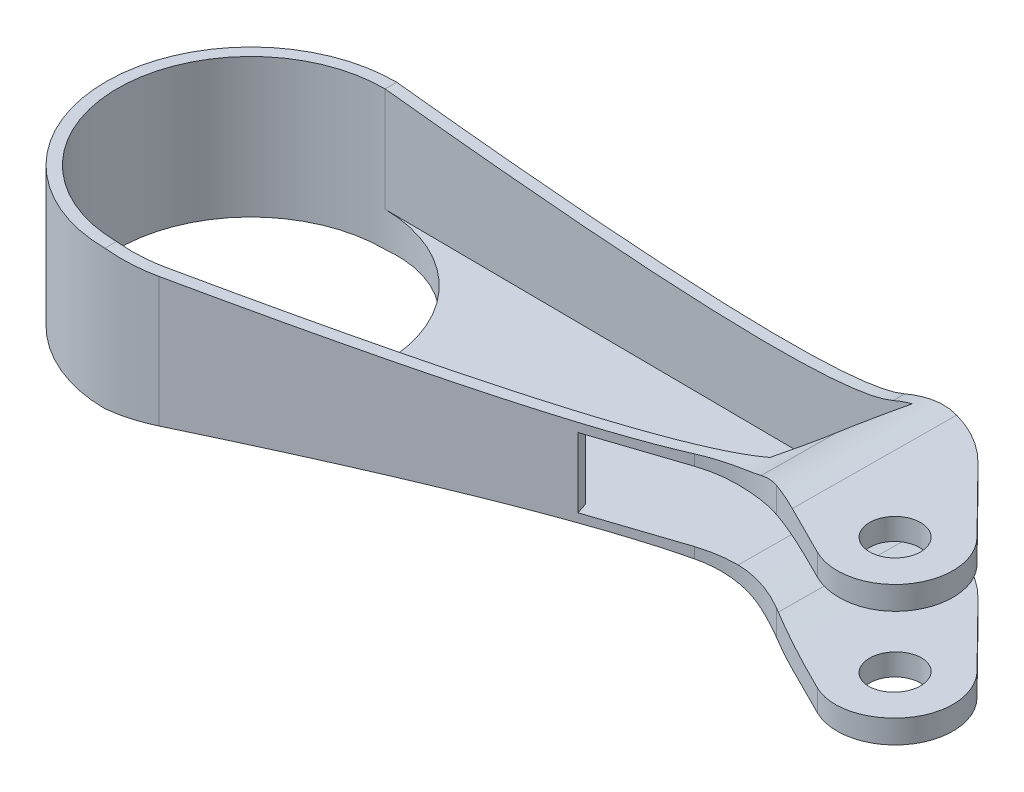
SolidWorks part; units mm, degrees
ref_plane "Front Plane" through (0, 0, 0) normal (0, 0, 1) x (1, 0, 0)
ref_plane "Top Plane" through (0, 0, 0) normal (0, 1, 0) x (1, 0, 0)
ref_plane "Right Plane" through (0, 0, 0) normal (1, 0, 0) x (0, 0, -1)
sketch "Sketch1" plane through (0, 0, 0) normal (0, 1, 0) x (1, 0, 0)
  line L0 (0, 0) -> (278, 0) construction
  line L1 (0, 0) -> (0, 62.5) construction
  line L2 (0.4822, 62.4981) -> (19.6718, -59.3235) construction
  line L3 (295.8135, 17.5408) -> (266.7848, -22.3432) construction
  line L4 (278, 0) -> (278, 25) construction
  line L5 (0.4822, 62.4981) -> (378.2559, 59.5837)
  line L6 (378.2559, 59.5837) -> (19.6718, -59.3235)
  line L7 (266.7848, -22.3432) -> (212.8435, 4.7326)
  line L8 (295.8135, 17.5408) -> (253.4664, 60.5464)
  line L9 (253.4664, 60.5464) -> (212.8435, 4.7326) construction
  circle A0 centre (0, 0) radius 62.5
  circle A1 centre (278, 0) radius 11
  circle A2 centre (278, 0) radius 25
  circle A3 centre (0, 0) radius 57.5
  point P11 (284.898, 28.626)
  dimension "D2" = 125
  dimension "D3" = 22
  dimension "D4" = 50
  dimension "D7" = 115
  dimension "D1" = 278
  dimension "D5" = 135
  dimension "D6" = 135
extrude "Boss-Extrude2" add sketch "Sketch1" along normal blind 30 and the other way blind 30 contours A0 A3 | A2 L8 L6 | A2 L6 L7 | A0 L6 L8 L5 | A2 A1 region at (142.126, 0, -22.2097) region at (43.1095, 0, -42.7782) region at (284.0848, 0, -25.2513) region at (241.7938, 0, -2.6298) region at (283.6909, 0, -23.6169)
fillet "Fillet1" radius 50 2 edges at (212.8435, 0, -4.7326) (253.4664, 0, -60.5464)
sketch "Sketch4" plane through (158.9581, 0, -156.5242) normal (0.7125, 0, -0.7016) x (-0.7016, 0, -0.7125)
  line L0 (-296.311, 0) -> (0, 0) construction
  line L1 (-179.7518, 87.9908) -> (-179.7518, -107.4173) construction
  line L2 (-120.0533, 10) -> (-120.0533, -10)
  line L3 (-120.0533, 10) -> (-276.8636, 10)
  line L4 (-120.0533, -10) -> (-276.8636, -10)
  line L5 (-276.8636, 10) -> (-276.8636, -10)
  line L6 (-120.0533, 30) -> (-120.0533, -30) construction
  dimension "D1" = 20
  dimension "D2" = 10
extrude "Cut-Extrude1" cut sketch "Sketch4" against normal blind 100
sketch "Sketch5" plane through (0, 30, 0) normal (0, 1, 0) x (1, 0, 0)
  line L0 (18.098, -54.5776) -> (213.7011, 10.2848)
  line L1 (229.7147, 55.7295) -> (213.7011, 10.2848)
  line L2 (193.1854, -1.786) -> (19.6718, -59.3235) construction
  line L3 (0.4436, 57.4983) -> (229.7147, 55.7295)
  line L5 (0.4822, 62.4981) -> (232.7563, 60.7062) construction
  arc A0 (0.4436, 57.4983) -> (0, -57.5) centre (0, 0) cw
  circle A1 centre (0, 0) radius 57.5 construction
  point P7 (213.8584, 9.8227)
  point P11 (0, 0)
  circle M11 centre (0, 0) radius 57.5
  dimension "D1" = 5
  dimension "D2" = 5
extrude "Cut-Extrude2" cut sketch "Sketch5" against normal blind 45 contours L3 L0 M11 region at (122.2864, 30, -19.5353)
sketch "Sketch6" plane through (0.4822, 0, -62.4981) normal (0.0077, 0, -1) x (-1, 0, -0.0077)
  line L0 (0, 0) -> (-302.9917, 0) construction
  line L1 (-227.281, -30) -> (-227.281, 30)
  line L2 (0, -30) -> (-232.281, -30) construction
  line L3 (0, 30) -> (-232.281, 30) construction
  line L4 (-302.9917, -42.13) -> (-302.9917, 48.7757) construction
  line L5 (-302.9917, -10) -> (-302.9917, -30) construction
  line L6 (-302.9917, -20) -> (-302.9917, 0)
  line L7 (-302.9917, 0) -> (-200.7772, 0)
  line L8 (-227.281, -30) -> (0, -30)
  line L10 (-302.9917, 20) -> (-302.9917, 0)
  line L11 (-302.9917, 0) -> (-200.7772, 0)
  line L12 (-232.281, 10) -> (-232.281, -10)
  line L13 (-227.281, 30) -> (0, 30)
  line L14 (-227.281, -10) -> (-227.281, 10) construction
  line L15 (-302.9917, 20) -> (-302.9917, 0)
  spline S0 degree 2 poles (-227.281, -30) (-216.527, -7.4312) (0, -30) knots 0 0 0 1 1 1
  spline S1 degree 3 poles (-302.9917, -20) (-266.3344, -19.1704) (-229.2326, -28.1121) (-200.7772, 0) knots 0 0 0 0 1 1 1 1
  spline S2 degree 2 poles (-227.281, 30) (-216.527, 7.4312) (0, 30) knots 0 0 0 1 1 1
  spline S3 degree 3 poles (-302.9917, 20) (-266.3344, 19.1704) (-229.2326, 28.1121) (-200.7772, 0) knots 0 0 0 0 1 1 1 1
  point P14 (-194.9918, 0)
  point P21 (-192.5089, 0)
  point P29 (-194.9918, 0)
  point P30 (-194.9918, 0)
  point P31 (-194.9918, 0)
  point P32 (-194.9918, 0)
  line M4 (0, 30) -> (-232.281, 30)
  line M6 (-232.281, 10) -> (-232.281, -10)
  dimension "D4" = 50
  dimension "D1" = 20
extrude "Cut-Extrude4" cut sketch "Sketch6" against normal blind 500 contours M4 | L11 L6 M6 | L10 L7 M6 | S0 L8 | L10 L11 S3 | L7 L6 S1 region at (134.696, 25.4862, -61.4627) region at (266.2411, -9.9605, -60.4479) region at (266.2411, 9.9605, -60.4479)
fillet "Fillet4" radius 60 4 edges at (227.5116, -30, -29.0067) (227.4699, 30, -23.6021) (213.6635, 10, -5.4092) (213.6635, -10, -5.4092)
fillet "Fillet7" radius 10 1 edges at (201.2341, 0, -58.4493)
sketch "Sketch9" plane through (186.8733, 0, 65.8495) normal (-0.9432, 0, -0.3323) x (-0.3323, 0, 0.9432)
  line L0 (-38.3586, -15) -> (-127.6676, -15)
  line L1 (-112.4851, -15) -> (-80.7227, -15) construction
  line L2 (-127.6676, -15) -> (-128.9063, 15)
  line L3 (-128.9063, 16.8023) -> (-128.9063, 27.8416) construction
  line L4 (-128.9063, 15) -> (-38.3586, 15)
  line L6 (-38.3586, 15) -> (-38.3586, -15)
  dimension "D1" = 30
extrude "Cut-Extrude7" cut sketch "Sketch9" against normal blind 500 and the other way blind 35 draft 20
sketch "Sketch10" plane through (18.098, 0, 54.5776) normal (-0.3147, 0, -0.9492) x (-0.9492, 0, 0.3147)
  line L0 (-206.0769, -15) -> (-143.079, -15)
  line L1 (0, -15) -> (-206.0769, -15) construction
  line L2 (-143.079, -15) -> (-143.079, 15)
  line L3 (-143.079, 15) -> (-206.0769, 15)
  line L4 (-206.0769, 15) -> (-206.0769, -15)
extrude "Cut-Extrude9" cut sketch "Sketch10" against normal blind 500
fillet "Fillet10" radius 100 2 edges at (224.096, 15, -19.3451) (224.1559, -15, -27.1096)
